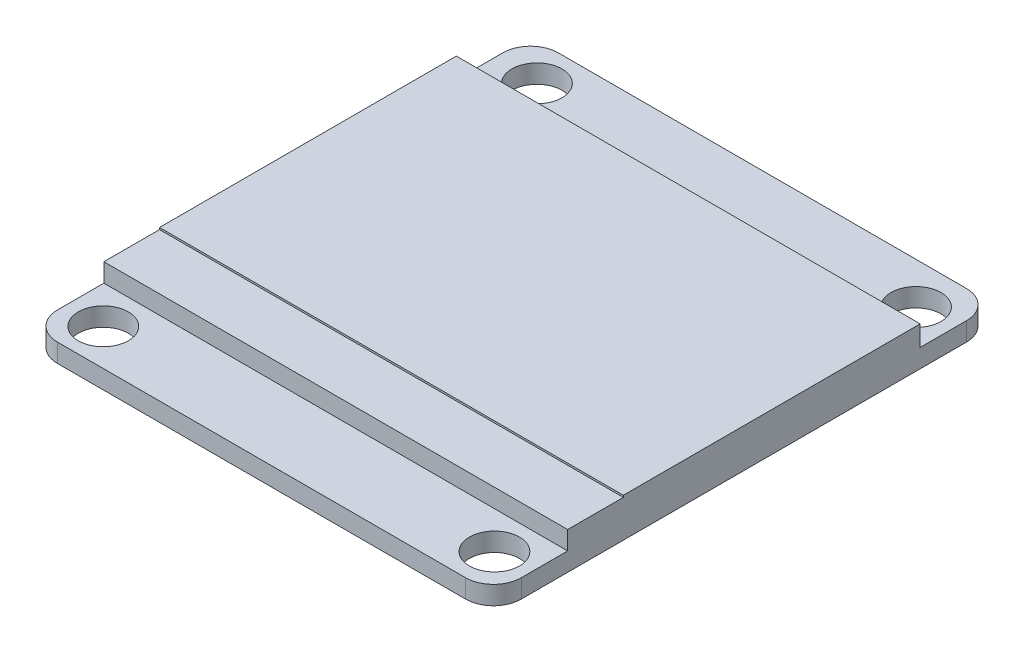
SolidWorks part; units mm, degrees
ref_plane "前视基准面" through (0, 0, 0) normal (0, 0, 1) x (1, 0, 0)
ref_plane "上视基准面" through (0, 0, 0) normal (0, 1, 0) x (1, 0, 0)
ref_plane "右视基准面" through (0, 0, 0) normal (1, 0, 0) x (0, 0, -1)
sketch "草图2" plane through (0, 0, 0) normal (0, 1, 0) x (1, 0, 0)
  line L1 (-118.2575, 92.3321) -> (-96.2575, 92.3321)
  line L2 (-119.7575, 90.8321) -> (-119.7575, 66.8321)
  line L3 (-118.2575, 65.3321) -> (-96.2575, 65.3321)
  line L4 (-94.7575, 90.8321) -> (-94.7575, 66.8321)
  arc A0 (-96.2575, 92.3321) -> (-94.7575, 90.8321) centre (-96.2575, 90.8321) cw
  arc A1 (-96.2575, 65.3321) -> (-94.7575, 66.8321) centre (-96.2575, 66.8321) ccw
  arc A2 (-119.7575, 66.8321) -> (-118.2575, 65.3321) centre (-118.2575, 66.8321) ccw
  arc A3 (-118.2575, 92.3321) -> (-119.7575, 90.8321) centre (-118.2575, 90.8321) ccw
  point P6 (-94.7575, 92.3321)
  point P9 (-94.7575, 65.3321)
  point P14 (-119.7575, 92.3321)
  dimension "D3" = 1.5
  dimension "D4" = 1.5
  dimension "D1" = 25
  dimension "D2" = 27
extrude "凸台-拉伸1" add sketch "草图2" along normal blind 1
sketch "草图3" plane through (0, 1, 0) normal (0, 1, 0) x (1, 0, 0)
  line L0 (-96.2575, 92.3321) -> (-118.2575, 92.3321) construction
  line L1 (-94.7575, 66.8321) -> (-94.7575, 90.8321) construction
  line L2 (-118.2575, 65.3321) -> (-96.2575, 65.3321) construction
  line L3 (-119.7575, 90.8321) -> (-119.7575, 66.8321) construction
  circle A0 centre (-117.413, 90.3321) radius 1.35
  circle A1 centre (-96.7575, 90.108) radius 1.35
  circle A2 centre (-96.7044, 67.3321) radius 1.35
  circle A3 centre (-117.7575, 67.3032) radius 1.35
  point P10 (0, 0)
  dimension "D5" = 2.7
  dimension "D1" = 2
  dimension "D2" = 2
  dimension "D3" = 2
  dimension "D4" = 2
extrude "切除-拉伸1" cut sketch "草图3" against normal blind 1
sketch "草图4" plane through (0, 1, 0) normal (0, 1, 0) x (1, 0, 0)
  line L0 (-119.7575, 90.8321) -> (-119.7575, 66.8321) construction
  line L1 (-119.7575, 88.3321) -> (-94.7575, 88.3321)
  line L2 (-119.7575, 88.3321) -> (-119.7575, 69.3321)
  line L3 (-119.7575, 69.3321) -> (-94.7575, 69.3321)
  line L4 (-94.7575, 88.3321) -> (-94.7575, 69.3321)
  line L5 (-94.7575, 66.8321) -> (-94.7575, 90.8321) construction
  line L6 (-96.2575, 92.3321) -> (-118.2575, 92.3321) construction
  dimension "D1" = 4
  dimension "D2" = 19
extrude "凸台-拉伸2" add sketch "草图4" along normal blind 1
sketch "草图5" plane through (0, 2, 0) normal (0, 1, 0) x (1, 0, 0)
  line L0 (-94.7575, 69.3321) -> (-94.7575, 88.3321) construction
  line L1 (-119.7575, 88.3321) -> (-94.7575, 88.3321)
  line L2 (-119.7575, 88.3321) -> (-119.7575, 72.3321)
  line L3 (-119.7575, 72.3321) -> (-94.7575, 72.3321)
  line L4 (-94.7575, 88.3321) -> (-94.7575, 72.3321)
  dimension "D1" = 16
extrude "凸台-拉伸3" add sketch "草图5" along normal blind 0.1
